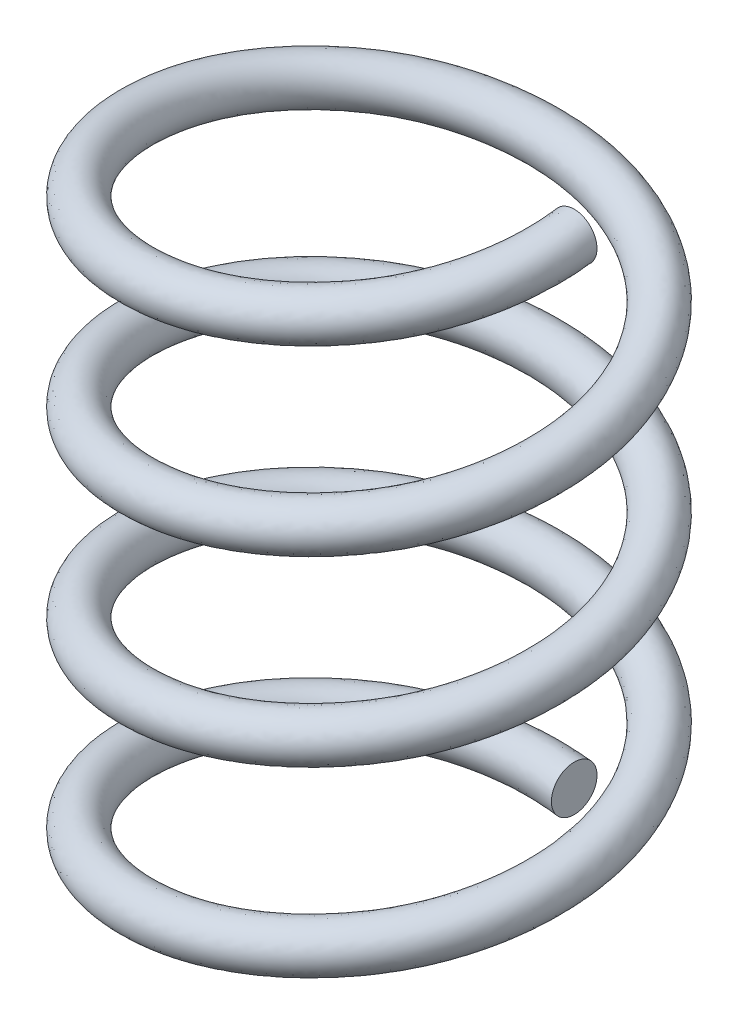
SolidWorks part; units mm, degrees
note: '?' marks a value the reader was unsure of.
material "AISI 304"
ref_plane "Front Plane" through (0, 0, 0) normal (0, 0, 1) x (1, 0, 0)
ref_plane "Top Plane" through (0, 0, 0) normal (0, 1, 0) x (1, 0, 0)
ref_plane "Right Plane" through (0, 0, 0) normal (1, 0, 0) x (0, 0, -1)
ref_axis "SpringAxis" through (0, 1.15, 0) along (0, -1, 0)?
sketch "SpringBodyDiameterS" plane through (0, 0, 0) normal (0, 0, 1) x (1, 0, 0)
  line L0 (0, 0) -> (1.6, 0) construction
  line L1 (0, 0) -> (0, 1) construction
  line L2 (1.8, 0) -> (2, 0) construction
  circle A0 centre (1.8, 0) radius 0.2
  dimension "WireDia" = 0.4
  dimension "RefRevolve" = 1
  dimension "RevolveDia" = 3.6
  dimension "RefID" = 3.2
  dimension "RefOD" = 4
sketch "SpringHelixS" plane through (0, 0, 0) normal (0, 1, 0) x (1, 0, 0)
  circle A0 centre (0, 0) radius 1.8
  dimension "RefDia" = 3.6
curve "SPRING HELIX" pitch 1.6 height 6 turns 3.75 parameters "Height"=6, "Pitch"=1.6
sweep "SPRING" add profiles "SpringBodyDiameterS" path "SPRING HELIX"
